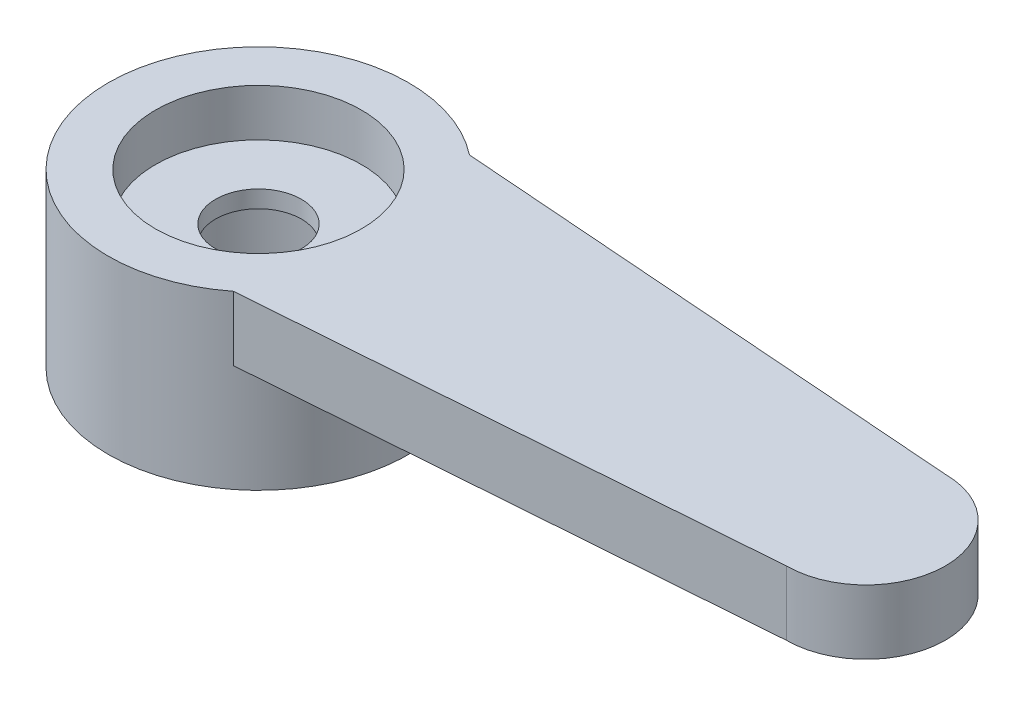
SolidWorks part; units mm, degrees
ref_plane "Спереди" through (0, 0, 0) normal (0, 0, 1) x (1, 0, 0)
ref_plane "Сверху" through (0, 0, 0) normal (0, 1, 0) x (1, 0, 0)
ref_plane "Справа" through (0, 0, 0) normal (1, 0, 0) x (0, 0, -1)
sketch "Эскиз1" plane through (0, 0, 0) normal (0, 1, 0) x (1, 0, 0)
  circle A0 centre (0, 0) radius 3.5
extrude "Бобышка-Вытянуть1" add sketch "Эскиз1" along normal blind 4
sketch "Эскиз2" plane through (0, 4, 0) normal (0, 1, 0) x (1, 0, 0)
  circle A0 centre (0, 0) radius 2.4
extrude "Вырез-Вытянуть1" cut sketch "Эскиз2" against normal blind 1.1
sketch "Эскиз3" plane through (0, 2.9, 0) normal (0, 1, 0) x (1, 0, 0)
  circle A0 centre (0, 0) radius 1
extrude "Вырез-Вытянуть2" cut sketch "Эскиз3" against normal through all
sketch "Эскиз4" plane through (0, 0, 0) normal (0, -1, 0) x (-1, 0, 0)
  circle A0 centre (0, 0) radius 2.3
extrude "Вырез-Вытянуть3" cut sketch "Эскиз4" against normal blind 2.5
sketch "Эскиз5" plane through (0, 4, 0) normal (0, 1, 0) x (1, 0, 0)
  line L0 (-3.5, 0) -> (16, 0) construction
  line L4 (14.15, 1.85) -> (2.1651, 2.75)
  line L5 (14.15, -1.85) -> (2.1651, -2.75)
  circle A0 centre (0, 0) radius 3.5 construction
  arc A1 (14.15, -1.85) -> (14.15, 1.85) centre (14.15, 0) ccw
  arc A2 (2.1651, -2.75) -> (2.1651, 2.75) centre (0, 0) ccw
  dimension "D1" = 19.5
extrude "Бобышка-Вытянуть2" add sketch "Эскиз5" against normal blind 1.5
